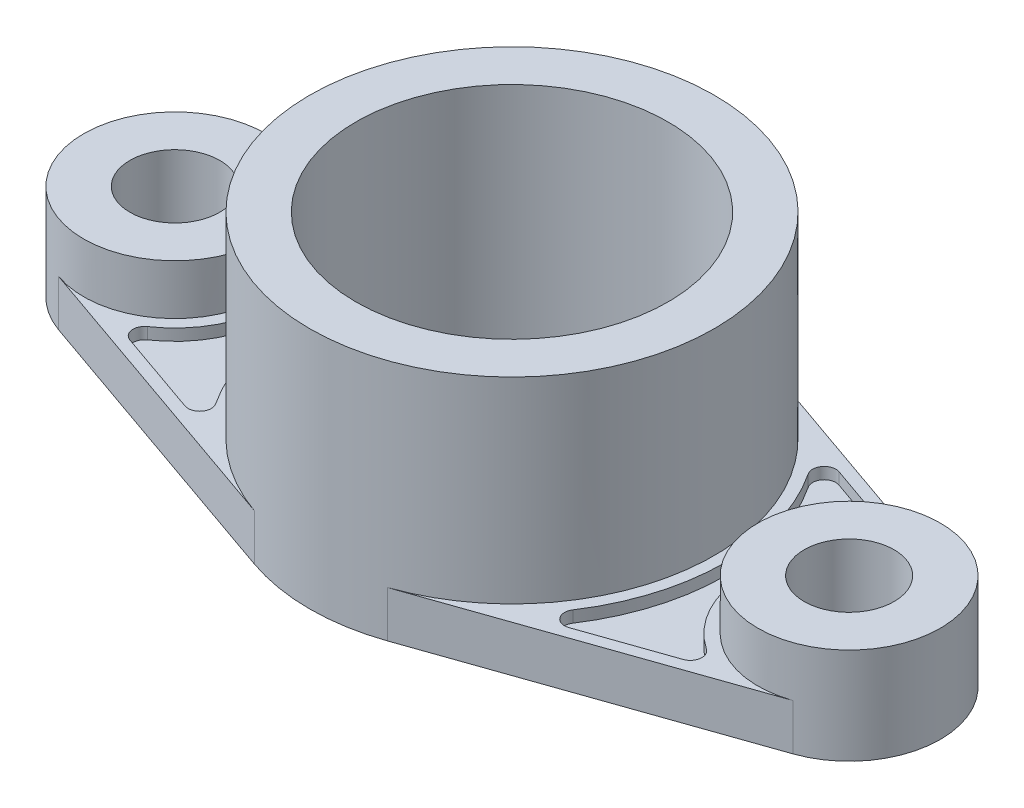
SolidWorks part; units mm, degrees
ref_plane "Front Plane" through (0, 0, 0) normal (0, 0, 1) x (1, 0, 0)
ref_plane "Top Plane" through (0, 0, 0) normal (0, 1, 0) x (1, 0, 0)
ref_plane "Right Plane" through (0, 0, 0) normal (1, 0, 0) x (0, 0, -1)
sketch "Sketch1" plane through (0, 0, 0) normal (0, 1, 0) x (1, 0, 0)
  line L0 (-95.2986, 22.3431) -> (-37.6098, 42.4788)
  line L1 (17.301, 49.5674) -> (95.2986, 22.3431)
  line L2 (95.2986, -22.3431) -> (17.301, -49.5674)
  line L3 (-95.2986, -22.3431) -> (-17.301, -49.5674)
  line L4 (-71.8093, 27.3643) -> (-49.826, 35.0373)
  line L5 (-71.8093, -27.3643) -> (-49.826, -35.0373)
  line L6 (49.826, -35.0373) -> (71.8093, -27.3643)
  line L7 (49.826, 35.0373) -> (71.8093, 27.3643)
  line L8 (-37.6098, 42.4788) -> (-18.0749, 49.2904)
  circle A0 centre (0, 0) radius 52.5
  circle A1 centre (0, 0) radius 40.5
  circle A2 centre (-87.5, 0) radius 11.665
  circle A3 centre (87.5, 0) radius 11.665
  circle A4 centre (-87.5, 0) radius 23.665
  circle A5 centre (87.5, 0) radius 23.665
  arc A6 (-46.3329, 30.5534) -> (-46.3329, -30.5534) centre (0, 0) ccw
  arc A7 (72.5075, 22.051) -> (72.5075, -22.051) centre (87.5, 0) ccw
  arc A8 (-72.5075, -22.051) -> (-72.5075, 22.051) centre (-87.5, 0) ccw
  arc A9 (72.5075, 22.051) -> (71.8093, 27.3643) centre (70.8207, 24.5319) ccw
  arc A10 (46.3329, -30.5534) -> (46.3329, 30.5534) centre (0, 0) ccw
  arc A11 (46.3329, 30.5534) -> (49.826, 35.0373) centre (48.8374, 32.2049) cw
  arc A12 (71.8093, -27.3643) -> (72.5075, -22.051) centre (70.8207, -24.5319) ccw
  arc A13 (49.826, -35.0373) -> (46.3329, -30.5534) centre (48.8374, -32.2049) cw
  arc A14 (-49.826, -35.0373) -> (-46.3329, -30.5534) centre (-48.8374, -32.2049) ccw
  arc A15 (-71.8093, -27.3643) -> (-72.5075, -22.051) centre (-70.8207, -24.5319) cw
  arc A16 (-72.5075, 22.051) -> (-71.8093, 27.3643) centre (-70.8207, 24.5319) cw
  arc A17 (-46.3329, 30.5534) -> (-49.826, 35.0373) centre (-48.8374, 32.2049) ccw
  point P26 (47.6905, -35.7827)
  point P27 (69.5443, -28.1549)
  point P28 (-70.8423, -27.7018)
  point P29 (-49.1079, -35.288)
  point P30 (-69.8084, 28.0627)
  point P31 (-49.8943, 35.0135)
  point P32 (43.2714, 37.3252)
  point P33 (65.7703, 29.4722)
  dimension "D1" = 105
  dimension "D2" = 12
  dimension "D3" = 23.33
  dimension "D4" = 23.33
  dimension "D5" = 12
  dimension "D6" = 12
  dimension "D9" = 3
  dimension "D10" = 3
  dimension "D11" = 3
  dimension "D21" = 3
  dimension "D22" = 3
  dimension "D23" = 3
  dimension "D7" = 87.5
  dimension "D8" = 87.5
  dimension "D12" = 3
  dimension "D13" = 3
  dimension "D14" = 3
  dimension "D15" = 3
  dimension "D16" = 3
  dimension "D17" = 3
  dimension "D18" = 3
  dimension "D19" = 3
  dimension "D20" = 20.6884
extrude "Boss-Extrude1" add sketch "Sketch1" along normal blind 12 contours A5 L1 A0 L2 L6 A13 A10 A11 L7 A9 A7 A12 region at (55.8841, 0, -34.7643)
extrude "Boss-Extrude2" add sketch "Sketch1<3>" along normal blind 9 contours A13 L6 A12 A7 A9 L7 A11 A10 | A6 A17 L4 A16 A8 A15 L5 A14 region at (-59.0698, 0, 0) region at (59.0698, 0, 0)
sketch "Sketch1<3>" plane through (0, 0, 0) normal (0, 1, 0) x (1, 0, 0) same geometry as "Sketch1"
extrude "Boss-Extrude3" add sketch "Sketch1<4>" along normal blind 12 contours A4 L3 A0 L8 L0 A17 A6 A14 L5 A15 A8 A16 L4 region at (-66.0392, 0, -31.2221)
sketch "Sketch1<4>" plane through (0, 0, 0) normal (0, 1, 0) x (1, 0, 0) same geometry as "Sketch1"
extrude "Boss-Extrude4" add sketch "Sketch1<5>" along normal blind 63 contours A0 A1 region at (-0.3994, 0, -51.0135)
sketch "Sketch1<5>" plane through (0, 0, 0) normal (0, 1, 0) x (1, 0, 0) same geometry as "Sketch1"
extrude "Boss-Extrude5" add sketch "Sketch1<6>" along normal blind 25 contours A5 A3 | A4 A2 region at (-74.1858, 0, -18.7492) region at (106.2492, 0, -13.3142)
sketch "Sketch1<6>" plane through (0, 0, 0) normal (0, 1, 0) x (1, 0, 0) same geometry as "Sketch1"
